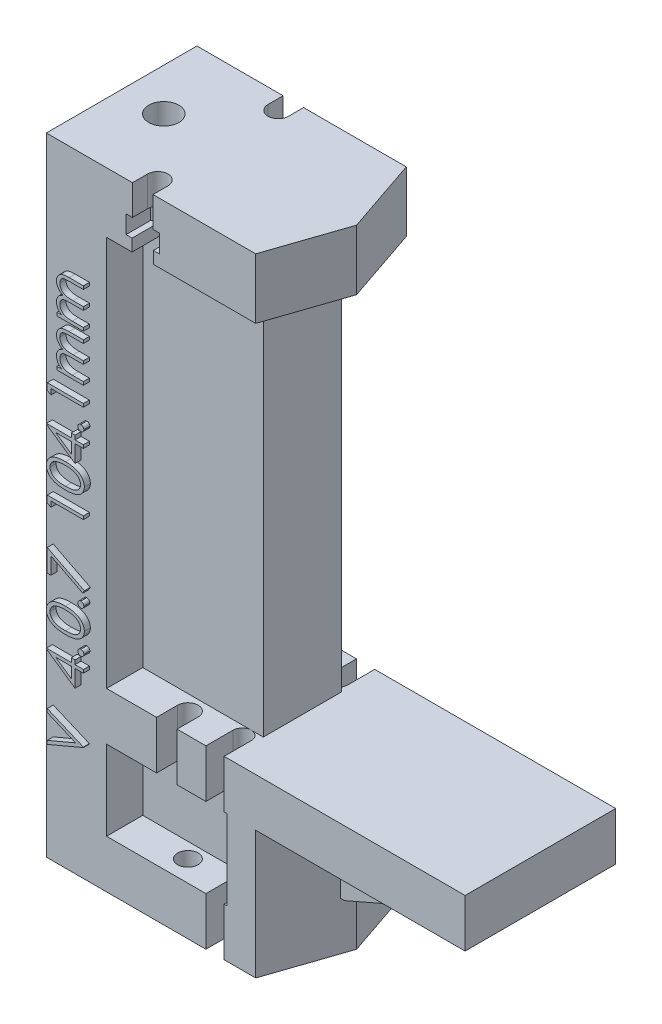
SolidWorks part; units mm, degrees
material "ABS"
ref_plane "Front" through (0, 0, 0) normal (0, 0, 1) x (1, 0, 0)
ref_plane "Top" through (0, 0, 0) normal (0, 1, 0) x (1, 0, 0)
ref_plane "Right" through (0, 0, 0) normal (1, 0, 0) x (0, 0, -1)
sketch "Sketch6" plane through (0, 0, 0) normal (0, 0, 1) x (1, 0, 0)
  line L0 (-25, 52.05) -> (15, 52.05)
  line L1 (15, 52.05) -> (15, 44.05)
  line L2 (15, 44.05) -> (-15, 44.05)
  line L3 (-15, 44.05) -> (-15, -44.05)
  line L4 (-15, -44.05) -> (25, -44.05)
  line L5 (25, -44.05) -> (25, -52.05)
  line L6 (25, -52.05) -> (-25, -52.05)
  line L7 (-25, -52.05) -> (-25, 52.05)
  line L8 (-25, 52.05) -> (25, -52.05) construction
  dimension "D1" = 104.1
  dimension "D2" = 8
  dimension "D3" = 10
  dimension "D4" = 50
  dimension "D5" = 40
extrude "Boss-Extrude2" add sketch "Sketch6" along normal mid plane 25
sketch "Sketch15" plane through (0, 0, 12.5) normal (0, 0, 1) x (1, 0, 0)
  line L0 (-15, -22.805) -> (15, -22.805)
  line L1 (-15, -44.05) -> (-15, 44.05) construction
  line L2 (-15, -30.805) -> (5, -30.805)
  line L3 (5, -52.05) -> (15, -52.05)
  line L4 (15, -52.05) -> (15, -22.805)
  line L5 (-25, -52.05) -> (25, -52.05) construction
  line L6 (-15, -30.805) -> (-15, -22.805)
  line L7 (5, -52.05) -> (5, -30.805)
  dimension "D2" = 8
extrude "Boss-Extrude3" add sketch "Sketch15" against normal up to surface (25 mm away) up to face at (0, 0, -12.5)
sketch "Sketch20" plane through (0, 52.05, 0) normal (0, 1, 0) x (1, 0, 0)
  line L0 (-10.7, 12.5) -> (-10.7, 10)
  line L1 (15, 12.5) -> (-25, 12.5) construction
  line L2 (-7.3, 10) -> (-7.3, 12.5)
  line L3 (-7.3, 12.5) -> (-10.7, 12.5)
  line L4 (0, 0) -> (15, 0) construction
  line L5 (15, -12.5) -> (15, 12.5) construction
  line L6 (-7.3, -12.5) -> (-10.7, -12.5)
  line L7 (-7.3, -10) -> (-7.3, -12.5)
  line L8 (-10.7, -12.5) -> (-10.7, -10)
  line L9 (-9, -10) -> (-9, 10) construction
  arc A0 (-10.7, 10) -> (-7.3, 10) centre (-9, 10) ccw
  arc A1 (-10.7, -10) -> (-7.3, -10) centre (-9, -10) cw
  dimension "D1" = 1.7
  dimension "D2" = 20
extrude "Cut-Extrude2" cut sketch "Sketch20" against normal up to next
sketch "Sketch21" plane through (0, -52.05, 0) normal (0, -1, 0) x (1, 0, 0)
  line L0 (-6.7, 12.5) -> (-6.7, 9)
  line L1 (-25, 12.5) -> (25, 12.5) construction
  line L2 (-3.3, 9) -> (-3.3, 12.5)
  line L3 (-3.3, 12.5) -> (-6.7, 12.5) construction
  line L4 (-5, -9) -> (-5, 9) construction
  line L5 (-6.7, 12.5) -> (-3.3, 12.5)
  line L7 (-3.3, -12.5) -> (-6.7, -12.5)
  line L8 (-3.3, -9) -> (-3.3, -12.5)
  line L9 (-6.7, -12.5) -> (-6.7, -9)
  arc A0 (-6.7, 9) -> (-3.3, 9) centre (-5, 9) ccw
  arc A1 (-6.7, -9) -> (-3.3, -9) centre (-5, -9) cw
  dimension "D1" = 1.7
  dimension "D2" = 18
extrude "Cut-Extrude3" cut sketch "Sketch21" against normal up to surface (29.245 mm away) up to face at (0, -22.805, 0)
sketch "Sketch22" plane through (0, 0, 0) normal (0, 0, 1) x (1, 0, 0)
  line L0 (-15, 21.805) -> (11, 44.05)
  line L1 (-7.3, 44.05) -> (15, 44.05) construction
  line L2 (-15, 44.05) -> (11, 44.05)
  line L5 (-15, -22.805) -> (-15, 44.05) construction
  line L7 (-15, 44.05) -> (-10.7, 44.05) construction
  line L8 (-15, 44.05) -> (-15, 21.805)
extrude "Boss-Extrude5" [suppressed] add sketch "Sketch22" along normal mid plane 4
sketch "Sketch23" plane through (0, 52.05, 0) normal (0, 1, 0) x (1, 0, 0)
  line L0 (-2.51, 12.5) -> (-2.51, 9)
  line L1 (15, 12.5) -> (-7.3, 12.5) construction
  line L2 (0.51, 9) -> (0.51, 12.5)
  line L3 (0.51, 12.5) -> (-2.51, 12.5)
  line L4 (-9, 10) -> (-1, 10) construction
  line L5 (-1, 10) -> (-1, 9) construction
  line L6 (0, 0) -> (12, 0) construction
  line L8 (0.51, -12.5) -> (-2.51, -12.5)
  line L9 (0.51, -9) -> (0.51, -12.5)
  line L10 (-2.51, -12.5) -> (-2.51, -9)
  line L11 (15, -12.5) -> (15, 12.5) construction
  arc A0 (-2.51, 9) -> (0.51, 9) centre (-1, 9) ccw
  arc A1 (-2.51, -9) -> (0.51, -9) centre (-1, -9) cw
  dimension "D1" = 1.51
  dimension "D2" = 8
  dimension "D3" = 1
  dimension "D4" = 3
extrude "Cut-Extrude4" [suppressed] cut sketch "Sketch23" against normal up to next
sketch "Sketch24" plane through (0, -52.05, 0) normal (0, -1, 0) x (1, 0, 0)
  line L0 (1.49, -12.5) -> (1.49, -8)
  line L1 (-3.3, -12.5) -> (25, -12.5) construction
  line L2 (4.51, -8) -> (4.51, -12.5)
  line L3 (4.51, -12.5) -> (1.49, -12.5)
  line L4 (3, -8) -> (3, -9) construction
  line L5 (3, -9) -> (-5, -9) construction
  line L9 (4.51, 12.5) -> (1.49, 12.5)
  line L10 (4.51, 8) -> (4.51, 12.5)
  line L11 (1.49, 12.5) -> (1.49, 8)
  arc A0 (1.49, -8) -> (4.51, -8) centre (3, -8) cw
  arc A1 (1.49, 8) -> (4.51, 8) centre (3, 8) ccw
  dimension "D2" = 8
  dimension "D3" = 1
extrude "Cut-Extrude6" cut sketch "Sketch24" against normal up to surface (29.245 mm away) up to face at (-3.3333, -22.805, 0)
sketch "Sketch28" plane through (0, 52.05, 0) normal (0, 1, 0) x (1, 0, 0)
  line L0 (-10.7, 10) -> (-7.3, 10) construction
  line L1 (-10.7, -10) -> (-7.3, -10) construction
  line L2 (-7.3, -12.5) -> (-7.3, -10) construction
  arc A0 (-10.7, 10) -> (-7.3, 10) centre (-9, 10) ccw construction
  arc A1 (-7.3, -10) -> (-10.7, -10) centre (-9, -10) ccw construction
sketch "Sketch29" plane through (-25, 0, 0) normal (-1, 0, 0) x (0, 0, 1)
  line L0 (-12.5, 52.05) -> (12.5, 52.05)
  line L1 (12.5, 52.05) -> (12.5, -52.05)
  line L2 (12.5, -52.05) -> (-12.9424, -52.05)
  line L3 (-12.9424, -52.05) -> (-12.5, 52.05)
extrude "Cut-Extrude7" [suppressed] cut sketch "Sketch29" against normal blind 6
sketch "Sketch30" plane through (0, -44.05, 0) normal (0, 1, 0) x (1, 0, 0)
  line L0 (25, 12.5) -> (25, -12.5)
  line L1 (25, -12.5) -> (15, -12.5)
  line L2 (15, -12.5) -> (15, 12.5)
  line L3 (15, 12.5) -> (25, 12.5)
extrude "Cut-Extrude8" cut sketch "Sketch30" against normal up to surface (8 mm away) up to face at (-0.8, -52.05, 0)
sketch "Sketch34" plane through (0, -22.805, 0) normal (0, 1, 0) x (1, 0, 0)
  line L1 (9.755, 12.5) -> (14, 0)
  line L2 (15, -12.5) -> (4.51, -12.5) construction
  line L3 (9.755, -12.5) -> (15, -12.5)
  line L6 (15, 12.5) -> (9.755, 12.5)
  line L7 (15, 12.5) -> (4.51, 12.5) construction
  line L9 (15, -12.5) -> (15, 12.5)
  line L10 (15, 0) -> (14, 0) construction
  line L11 (14, 0) -> (9.755, -12.5)
extrude "Cut-Extrude9" cut sketch "Sketch34" against normal through all both and the other way through all
sketch "Sketch35" plane through (0, 0, 12.5) normal (0, 0, 1) x (1, 0, 0)
  line L0 (-17.85, 52.05) -> (-17.85, -52.05) construction
  line L1 (-10.7, 52.05) -> (-25, 52.05) construction
  line L2 (-25, -52.05) -> (-6.7, -52.05) construction
  text T0 "V  4.0.7  104.1mm" font "Century Gothic" height 6
extrude "Boss-Extrude6" add sketch "Sketch35" along normal blind 1
sketch3d "3DSketch1"
  line L0 (4.51, -22.805, 12.5) -> (4.51, -30.805, 12.5)
  line L1 (4.51, -30.805, 12.5) -> (4.51, -30.805, -12.5)
  line L2 (4.51, -30.805, -12.5) -> (4.51, -22.805, -12.5)
  line L3 (4.51, -22.805, -12.5) -> (4.51, -22.805, 12.5)
extrude "Boss-Extrude7" add sketch "3DSketch1" along direction (1, 0, 0) on the side against the normal blind 40
sketch "Sketch37" plane through (0, 0, 0) normal (0, 0, 1) x (1, 0, 0)
  line L1 (14, -30.805) -> (44.51, -30.805)
  line L3 (5, -44.05) -> (14, -44.05) construction
  line L4 (14, -30.805) -> (14, -44.05)
  line L5 (14, -44.05) -> (44.51, -30.805)
extrude "Boss-Extrude17" add sketch "Sketch37" along direction (0, 0, 1) on the side of the normal mid plane 4 separate body
sketch "Sketch38" plane through (0, 44.05, 0) normal (0, -1, 0) x (1, 0, 0)
  line L0 (-11.75, 11.5877) -> (-11.75, 12.5) construction
  line L1 (-10.7, 10) -> (-7.3, 10) construction
  line L2 (-6.25, 8.4123) -> (-6.25, 11.5877) construction
  line L3 (-9, 6.8246) -> (-6.25, 8.4123)
  line L4 (-11.75, 8.4123) -> (-9, 6.8246)
  line L5 (-11.75, 11.5877) -> (-11.75, 8.4123) construction
  line L6 (-9, 13.1754) -> (-11.75, 11.5877) construction
  line L7 (-6.25, 11.5877) -> (-9, 13.1754) construction
  line L8 (-10.7, -10) -> (-7.3, -10) construction
  line L9 (-6.25, -11.5877) -> (-6.25, -8.4123) construction
  line L10 (-6.25, -8.4123) -> (-9, -6.8246)
  line L11 (-9, -6.8246) -> (-11.75, -8.4123)
  line L12 (-11.75, -8.4123) -> (-11.75, -11.5877) construction
  line L13 (-11.75, -11.5877) -> (-9, -13.1754) construction
  line L14 (-9, -13.1754) -> (-6.25, -11.5877) construction
  line L15 (-15, 12.5) -> (-10.7, 12.5) construction
  line L17 (-7.3, 12.5) -> (9.755, 12.5) construction
  line L18 (-6.25, 12.5) -> (-6.25, 11.5877) construction
  line L19 (-11.75, -11.5877) -> (-11.75, -12.5) construction
  line L20 (-15, -12.5) -> (-10.7, -12.5) construction
  line L21 (-11.77, -12.5) -> (-6.23, -12.5)
  line L22 (-7.3, -12.5) -> (9.755, -12.5) construction
  line L23 (-6.25, -12.5) -> (-6.25, -11.5877) construction
  line L24 (-11.77, 12.5) -> (-11.77, 8.4238)
  line L25 (-11.77, 8.4238) -> (-11.75, 8.4123)
  line L26 (-6.23, 12.5) -> (-6.23, 8.4238)
  line L27 (-6.23, 8.4238) -> (-6.25, 8.4123)
  line L28 (-11.77, 12.5) -> (-6.23, 12.5)
  line L29 (-6.25, -8.4123) -> (-6.23, -8.4238)
  line L30 (-6.23, -8.4238) -> (-6.23, -12.5)
  line L31 (-11.77, -12.5) -> (-11.77, -8.4238)
  line L32 (-11.77, -8.4238) -> (-11.75, -8.4123)
  circle A1 centre (-9, 10) radius 2.75 construction
  circle A2 centre (-9, 10) radius 3.1754 construction
  circle A3 centre (-9, -10) radius 3.1754 construction
  circle A4 centre (-9, -10) radius 2.75 construction
  point P18 (-6.25, -10)
  point P19 (-9, 10)
  point P24 (-7.625, -7.6184)
  point P25 (-10.375, -7.6184)
  dimension "D1" = 5.5
  dimension "D2" = 6
  dimension "D3" = 6.3509
  dimension "D4" = 5.5
  dimension "D5" = 6.3509
  dimension "D7" = 0.02
  dimension "D8" = 0.02
  dimension "D9" = 0.02
extrude "Cut-Extrude10" cut sketch "Sketch38" against normal blind 3
sketch "Sketch39" plane through (14, 0, 0) normal (-1, 0, 0) x (0, 0, 1)
  line L1 (-2, -44.05) -> (2, -44.05)
  line L2 (-2, -44.05) -> (-2, -30.805)
  line L3 (-2, -30.805) -> (2, -30.805)
  line L4 (2, -44.05) -> (2, -30.805)
extrude "Boss-Extrude18" add sketch "Sketch39" along normal blind 2.5
hole_wizard "Ø5.0mm Dowel Hole1" positions "Sketch41" profile "Sketch42" hole size "Ø5.0" standard "ANSI Metric"
sketch "Sketch41" plane through (0, 52.05, 0) normal (0, 1, 0) x (1, 0, 0)
  line L0 (-25, 0) -> (-18, 0) construction
  line L1 (-25, -12.5) -> (-25, 12.5) construction
  point P0 (-18, 0)
  dimension "D1" = 7
sketch "Sketch42" plane through (-18, 52.05, 0) normal (1, 0, 0) x (0, 0, 1)
  line L0 (0, 0) -> (0, 6.5022)
  line L1 (0, 6.5022) -> (2.5, 5)
  line L2 (2.5, 5) -> (2.5, 0)
  line L5 (2.5, 0) -> (0, 0)
  line L10 (0, 6.5022) -> (-2.5, 5) construction
  line L11 (0, -6.35) -> (0, 107.95) construction
  dimension "Hole Dia." = 5
  dimension "Hole Depth" = 5
  dimension "Drill Angle" = 118
sketch "Sketch43" plane through (0, 44.05, 0) normal (0, -1, 0) x (1, 0, 0)
  line L0 (-11.77, 12.5) -> (-10.77, 12.5)
  line L1 (-10.77, 12.5) -> (-10.77, 7.8465)
  line L2 (-6.23, 12.5) -> (-7.23, 12.5)
  line L3 (-7.23, 12.5) -> (-7.23, 7.8465)
  line L4 (-11.77, -12.5) -> (-10.77, -12.5)
  line L5 (-10.77, -12.5) -> (-10.77, -7.8465)
  line L6 (-6.23, -12.5) -> (-7.23, -12.5)
  line L7 (-7.23, -12.5) -> (-7.23, -7.8465)
  line L8 (5, 2) -> (5, -2)
  line L19 (-15, -12.5) -> (-11.77, -12.5)
  line L20 (-11.77, 8.4238) -> (-11.77, 12.5)
  line L21 (-11.77, -8.4238) -> (-9, -6.8246)
  line L22 (-9, -6.8246) -> (-6.23, -8.4238)
  line L23 (-11.77, 8.4238) -> (-11.77, 12.5)
  line L24 (-6.23, -12.5) -> (9.755, -12.5)
  line L25 (-6.23, -12.5) -> (9.755, -12.5)
  line L26 (9.755, -12.5) -> (14, 0)
  line L27 (9.755, -12.5) -> (14, 0)
  line L28 (-11.77, -12.5) -> (-11.77, -8.4238)
  line L29 (-6.23, 8.4238) -> (-9, 6.8246)
  line L30 (-9, 6.8246) -> (-11.77, 8.4238)
  line L31 (-11.77, -12.5) -> (-11.77, -8.4238)
  line L32 (-11.77, 12.5) -> (-15, 12.5)
  line L33 (-15, 12.5) -> (-15, -12.5)
  line L38 (-15, -12.5) -> (-11.77, -12.5)
  line L40 (-11.77, -8.4238) -> (-9, -6.8246)
  line L41 (-9, -6.8246) -> (-6.23, -8.4238)
  line L48 (-6.23, 8.4238) -> (-9, 6.8246)
  line L49 (-9, 6.8246) -> (-11.77, 8.4238)
  line L51 (-11.77, 12.5) -> (-15, 12.5)
  line L52 (-15, 12.5) -> (-15, -12.5)
  line L57 (-6.23, -8.4238) -> (-6.23, -12.5)
  line L58 (-6.23, -8.4238) -> (-6.23, -12.5)
  line L59 (-6.23, 12.5) -> (-6.23, 8.4238)
  line L60 (-6.23, 12.5) -> (-6.23, 8.4238)
  line L61 (14, 0) -> (9.755, 12.5)
  line L62 (14, 0) -> (9.755, 12.5)
  line L64 (9.755, 12.5) -> (-6.23, 12.5)
  line L65 (9.755, 12.5) -> (-6.23, 12.5)
  dimension "D2" = 1
  dimension "D3" = 1
  dimension "D4" = 1
  dimension "D5" = 1
  dimension "D1" = 0
extrude "Boss-Extrude19" add sketch "Sketch43" along normal blind 2
sketch "Sketch44" plane through (0, -52.05, 0) normal (0, -1, 0) x (1, 0, 0)
  line L0 (-6.7, -9) -> (-6.7, -12.5)
  line L1 (-6.7, -12.5) -> (-3.3, -12.5)
  line L2 (-3.3, -12.5) -> (-3.3, -9)
  line L3 (-6.7, 9) -> (-6.7, 12.5)
  line L4 (-6.7, 12.5) -> (-3.3, 12.5)
  line L5 (-3.3, 12.5) -> (-3.3, 9)
  circle A0 centre (-5, -9) radius 1.7
  circle A1 centre (-5, 9) radius 1.7
  line M8 (-3.3, 12.5) -> (-3.3, 9)
  line M10 (-6.7, 9) -> (-6.7, 12.5)
  line M14 (-6.7, -12.5) -> (-6.7, -9)
  line M16 (-3.3, -9) -> (-3.3, -12.5)
extrude "Boss-Extrude20" add sketch "Sketch44" against normal up to surface (8 mm away) contours A1 L4 M8 M10 | A0 L1 M14 M16
sketch "Sketch45" plane through (0, -22.805, 0) normal (0, 1, 0) x (1, 0, 0)
  line L0 (-15, 12.5) -> (-15, -12.5) construction
  line L1 (-15, -6.49) -> (5, -6.49)
  line L2 (-15, -6.49) -> (-15, 6.49)
  line L3 (-15, 6.49) -> (5, 6.49)
  line L4 (5, -6.49) -> (5, 6.49)
  line L5 (5, -6.49) -> (5, 6.49) construction
  line L7 (5, -12.5) -> (5, 12.5) construction
  arc A0 (1.49, 8) -> (4.51, 8) centre (3, 8) ccw construction
  arc A1 (4.51, -8) -> (1.49, -8) centre (3, -8) ccw construction
extrude "Boss-Extrude21" add sketch "Sketch45" along normal up to next and the other way up to surface other way up to face at (0.3333, -44.05, 0)
ref_plane "Plane1" through (-25, 52.05, 12.5) normal (0, 0, -1) x (-1, 0, 0)
sketch "Sketch47" plane through (0, 52.05, 0) normal (0, 1, 0) x (1, 0, 0)
  line L1 (-50.4654, -28.787) -> (42.0947, -28.787)
  line L2 (-50.4654, -28.787) -> (-50.4654, 26.08)
  line L3 (-50.4654, 26.08) -> (42.0947, 26.08)
  line L4 (42.0947, -28.787) -> (42.0947, 26.08)
